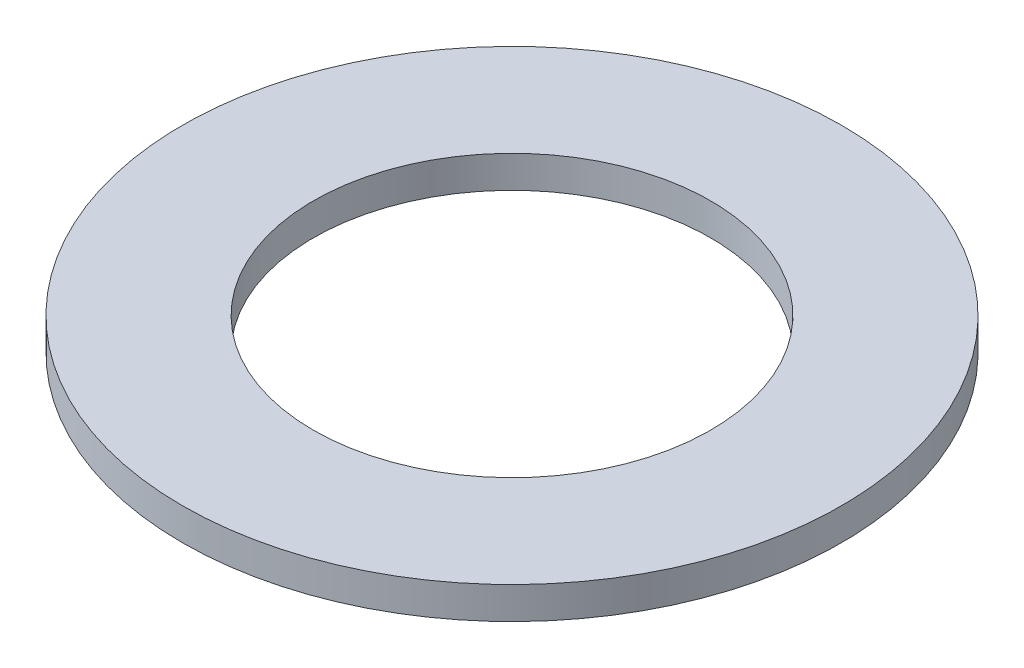
SolidWorks part; units mm, degrees
ref_plane "Front Plane" through (0, 0, 0) normal (0, 0, 1) x (1, 0, 0)
ref_plane "Top Plane" through (0, 0, 0) normal (0, 1, 0) x (1, 0, 0)
ref_plane "Right Plane" through (0, 0, 0) normal (1, 0, 0) x (0, 0, -1)
sketch "Sketch1" plane through (0, 0, 0) normal (0, 1, 0) x (1, 0, 0)
  circle A0 centre (0, 0) radius 82.2
  circle A1 centre (0, 0) radius 49.55
  dimension "D1" = 164.4
  dimension "D2" = 99.1
extrude "Boss-Extrude1" add sketch "Sketch1" along normal blind 8
